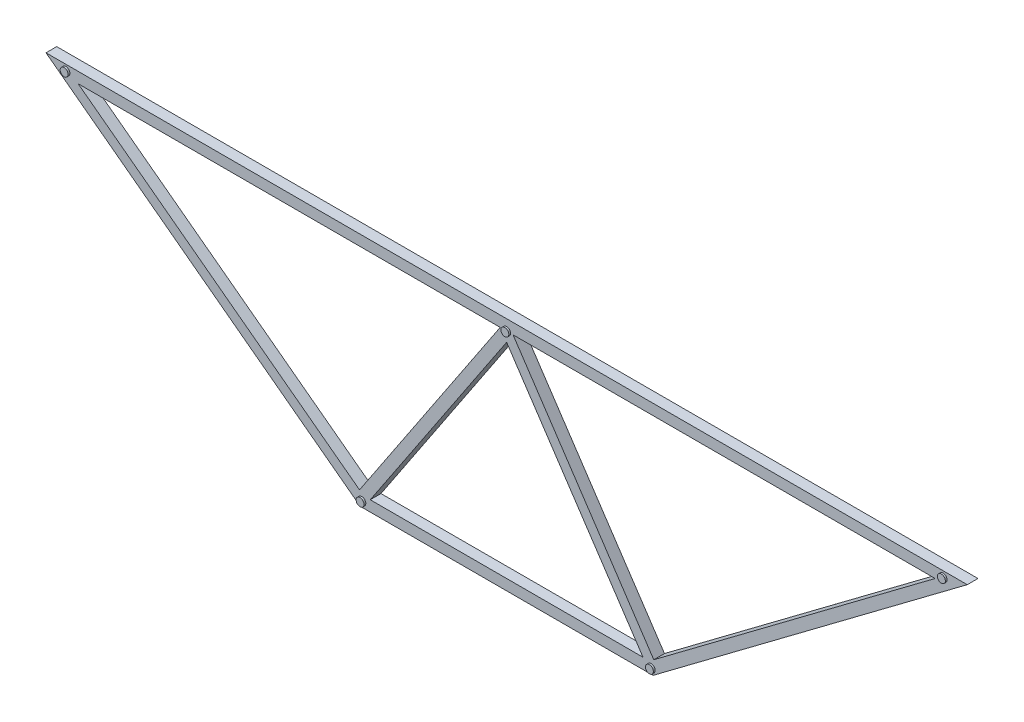
SolidWorks part; units mm, degrees
other "Truss Body"
other "Pin E"
other "Pin A"
other "Pin D"
other "Pin C"
other "Pin B"
material "A500"
ref_plane "Front Plane" through (0, 0, 0) normal (0, 0, 1) x (1, 0, 0)
ref_plane "Top Plane" through (0, 0, 0) normal (0, 1, 0) x (1, 0, 0)
ref_plane "Right Plane" through (0, 0, 0) normal (1, 0, 0) x (0, 0, -1)
sketch "Sketch22" plane through (0, 0, 0) normal (0, 0, 1) x (1, 0, 0)
  line L0 (0, 0) -> (600, 0)
  line L1 (600, 0) -> (1200, 0)
  line L4 (400, -300) -> (800, -300)
  line L5 (-45, 15) -> (600, 15)
  line L6 (0, 0) -> (400, -300)
  line L9 (1200, 0) -> (800, -300)
  line L10 (-45, 15) -> (395, -315)
  line L13 (600, 15) -> (1245, 15)
  line L14 (1245, 15) -> (805, -315)
  line L16 (395, -315) -> (805, -315)
  line L18 (590.9861, 0) -> (393.9907, -295.4931)
  line L19 (600, -13.5208) -> (790.9861, -300)
  line L20 (609.0139, 0) -> (806.0093, -295.4931)
  line L22 (600, -13.5208) -> (409.0139, -300)
extrude "Truss Body." add sketch "Sketch22" along normal blind 15 contours L10 L16 L14 L13 L5 L1 L9 L4 L6 L0 | L22 L19 L4 L9 L20 L1 L0 L18 L6 region at (595.4931, -5.0967, 0) region at (277.5, 1.6846, 0)
sketch "Sketch25" plane through (0, 0, 15) normal (0, 0, 1) x (1, 0, 0)
  circle A0 centre (-17.1152, 6.7128) radius 5.555
  circle A1 centre (397.2568, -307.5532) radius 5.555
  circle A2 centre (802.3949, -307.5532) radius 5.555
  circle A3 centre (1211.2073, 6.7128) radius 5.555
  circle A4 centre (600, 0) radius 5.555
  dimension "D1" = 11.11
  dimension "D2" = 11.11
  dimension "D3" = 11.11
  dimension "D4" = 11.11
  dimension "D5" = 11.11
extrude "Pin Holes" cut sketch "Sketch25" against normal through all
sketch "Sketch27" plane through (0, 0, 15) normal (0, 0, 1) x (1, 0, 0)
  circle A0 centre (-17.1152, 6.7128) radius 5.555
  circle A1 centre (397.2568, -307.5532) radius 5.555
  circle A2 centre (802.3949, -307.5532) radius 5.555
  circle A3 centre (600, 0) radius 5.555
  circle A4 centre (1211.2073, 6.7128) radius 5.555
sketch "Sketch29" plane through (0, 0, 15) normal (0, 0, 1) x (1, 0, 0)
  circle A0 centre (-17.1152, 6.7128) radius 5.555
  circle A1 centre (397.2568, -307.5532) radius 5.555
  circle A2 centre (802.3949, -307.5532) radius 5.555
  circle A3 centre (1211.2073, 6.7128) radius 5.555
  circle A4 centre (600, 0) radius 5.555
extrude "Boss-Extrude10" add sketch "Sketch29" against normal blind 17.5 and the other way blind 2.5 separate body
